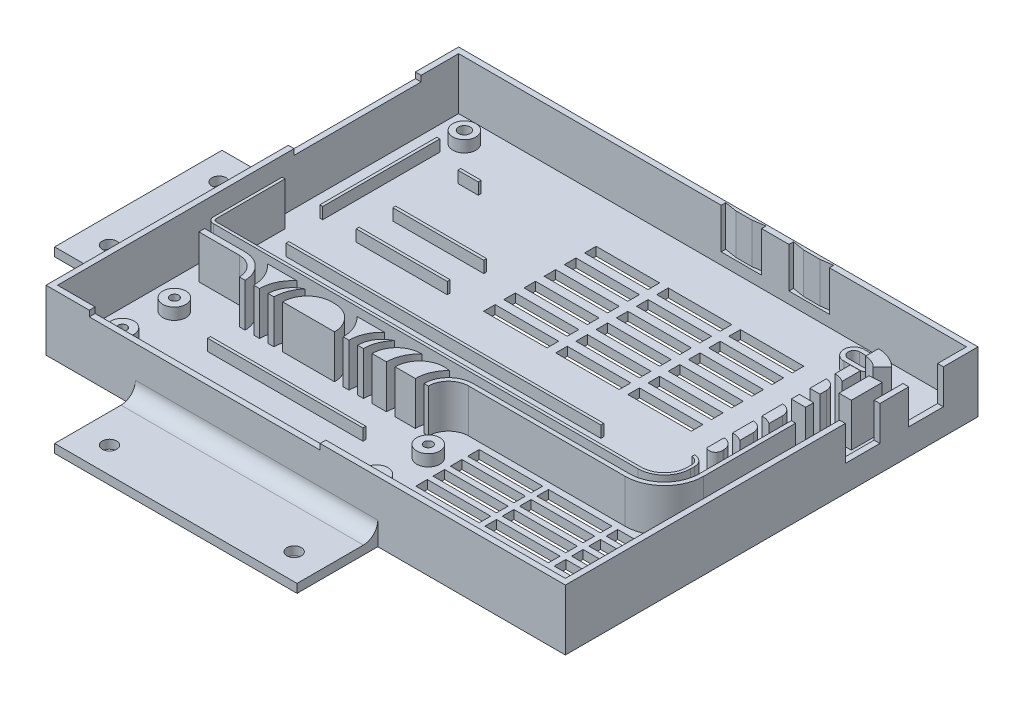
SolidWorks part; units mm, degrees
ref_plane "Front Plane" through (0, 0, 0) normal (0, 0, 1) x (1, 0, 0)
ref_plane "Top Plane" through (0, 0, 0) normal (0, 1, 0) x (1, 0, 0)
ref_plane "Right Plane" through (0, 0, 0) normal (1, 0, 0) x (0, 0, -1)
sketch "Sketch1" plane through (0, 0, 0) normal (0, 1, 0) x (1, 0, 0)
  line L0 (-67.5, 0) -> (67.5, 0) construction
  line L1 (0, 38) -> (0, -38) construction
  line L3 (-67.5, 38) -> (67.5, 38) construction
  line L4 (-67.5, 38) -> (-67.5, -38) construction
  line L5 (-67.5, -38) -> (67.5, -38) construction
  line L6 (67.5, 38) -> (67.5, -38) construction
  line L7 (-67.5, 38) -> (67.5, -38) construction
  line L8 (-67.5, -38) -> (67.5, 38) construction
  line L9 (-71, -71.5) -> (24, -71.5) construction
  line L10 (-23.5, -59) -> (-23.5, -84) construction
  line L11 (-38, -59) -> (-38, -71.5) construction
  line L12 (-17, -59) -> (-17, -71.5) construction
  line L13 (11, -59) -> (11, -71.5) construction
  line L14 (-79.5, 48) -> (-79.5, -95) construction
  line L16 (24, -59) -> (24, -84) construction
  line L17 (-79.5, -95) -> (100.5, -95) construction
  line L18 (100.5, -95) -> (100.5, 48) construction
  line L19 (-71, -59) -> (-71, -84) construction
  line L20 (-71, -84) -> (24, -84) construction
  line L21 (100.5, 48) -> (-79.5, 48) construction
  line L22 (-71, -59) -> (24, -59) construction
  line L23 (0, 38) -> (0, 42) construction
  line L24 (-71.5, 42) -> (71.5, 42) construction
  line L25 (-71.5, 42) -> (-71.5, -42) construction
  line L26 (-71.5, -42) -> (71.5, -42) construction
  line L27 (71.5, 42) -> (71.5, -42) construction
  line L28 (-67.5, 0) -> (-71.5, 0) construction
  line L29 (-43, -59) -> (-43, -71.5) construction
  line L30 (-48, -59) -> (-48, -71.5) construction
  line L31 (-12, -59) -> (-12, -71.5) construction
  line L32 (-7, -59) -> (-7, -71.5) construction
  line L33 (1, -59) -> (1, -71.5) construction
  line L34 (67.5, 38) -> (72.7, 38) construction
  line L35 (67.5, 40) -> (72.7, 40)
  line L36 (67.5, 36) -> (72.7, 36)
  line L37 (67.5, -38) -> (72.6846, -38.4) construction
  line L40 (67.6538, -36.0059) -> (72.8384, -36.4059)
  line L41 (67.3462, -39.9941) -> (72.5307, -40.3941)
  line L42 (-67.5, -38) -> (-67.5, -38.4) construction
  line L43 (-65.5, -38) -> (-65.5, -38.4)
  line L44 (-69.5, -38) -> (-69.5, -38.4)
  circle A0 centre (-67.5, 38) radius 2
  circle A4 centre (-67.5, -62.5) radius 1.5
  circle A8 centre (20.5, -62.5) radius 1.5
  circle A9 centre (20.5, -80.5) radius 1.5
  circle A10 centre (-67.5, -80.5) radius 1.5
  arc A11 (67.5, 40) -> (67.5, 36) centre (67.5, 38) ccw
  arc A12 (72.7, 36) -> (72.7, 40) centre (72.7, 38) ccw
  arc A15 (67.6538, -36.0059) -> (67.3462, -39.9941) centre (67.5, -38) ccw
  arc A16 (72.5307, -40.3941) -> (72.8384, -36.4059) centre (72.6846, -38.4) ccw
  arc A17 (-65.5, -38) -> (-69.5, -38) centre (-67.5, -38) ccw
  arc A18 (-69.5, -38.4) -> (-65.5, -38.4) centre (-67.5, -38.4) ccw
  point P5 (0, 0)
  point P11 (70.1, 38)
  point P13 (-67.5, -38.2)
  point P14 (-23.5, -70)
  point P27 (0, 0)
  point P62 (70.0923, -38.2)
  dimension "D3" = 4
  dimension "D6" = 84
  dimension "D1" = 76
  dimension "D2" = 135
  dimension "D4" = 18
  dimension "D5" = 88
  dimension "D7" = 143
  dimension "D8" = 25
  dimension "D9" = 95
  dimension "D10" = 17
  dimension "D11" = 28
  dimension "D12" = 33
  dimension "D13" = 54
  dimension "D14" = 82
  dimension "D15" = 14.5
  dimension "D16" = 10
  dimension "D17" = 12
  dimension "D18" = 33
  dimension "D19" = 23
  dimension "D20" = 59
  dimension "D21" = 64
  dimension "D22" = 72
  dimension "D23" = 5.2
  dimension "D24" = 4
  dimension "D25" = 4
  dimension "D26" = 5.2
  dimension "D27" = 4
  dimension "D28" = 0.4
  dimension "D29" = 0.4
sketch "CablePath" plane through (0, 0, 0) normal (0, 1, 0) x (1, 0, 0)
  line L0 (-12, -59) -> (-12, -56) construction
  line L5 (101, -94.5) -> (101, 47)
  line L6 (101, 47) -> (-79, 47)
  line L8 (-43, -56) -> (-43, -70.139) construction
  line L9 (-75.5, -42.5222) -> (-75.5, -18.6789) construction
  line L12 (71.5, -29) -> (80.8048, -29) construction
  line L16 (-71.5, -42) -> (71.5, -42) construction
  line L18 (71.5, -18.84) -> (80.8048, -18.84) construction
  line L21 (80.8048, -51.7714) -> (80.8048, 34.0145) construction
  line L22 (30.5, -56) -> (-60.9203, -56) construction
  line L23 (-10.5, -56) -> (-8.5, -56)
  line L24 (71.5, 40.5) -> (71.5, -42) construction
  line L25 (1, -59) -> (1, -56) construction
  line L26 (85.8048, -3.52) -> (85.8048, -35.359) construction
  line L27 (-79, 47) -> (-79, -94.5)
  line L28 (11, -59) -> (11, -56) construction
  line L29 (-79, -94.5) -> (101, -94.5)
  line L30 (-38, -70.139) -> (-38, -56) construction
  line L31 (-43, -59) -> (-43, -71.5) construction
  line L32 (-38, -59) -> (-38, -71.5) construction
  line L33 (71.5, 1.48) -> (80.8048, 1.48) construction
  line L34 (-58, -44.5) -> (-72.0222, -44.5)
  line L35 (75.1637, -46) -> (-33, -46) construction
  line L36 (84.3048, -3.52) -> (84.3048, -8.2028)
  line L37 (-71, -59) -> (24, -59) construction
  line L38 (75.1637, -44.5) -> (-33, -44.5)
  line L39 (71.5, -8.68) -> (80.8048, -8.68) construction
  line L40 (87.3048, -3.52) -> (87.3048, -35.359)
  line L41 (21, -47.5) -> (75.1637, -47.5)
  line L42 (84.3048, -13.68) -> (84.3048, -18.3628)
  line L43 (84.3048, -23.84) -> (84.3048, -24.2165)
  line L44 (84.3048, -3.52) -> (84.3048, -35.359) construction
  line L45 (84.3048, -34) -> (84.3048, -35.359)
  line L46 (-27.8976, -47.4999) -> (-26.899, -47.4999)
  line L47 (75.1637, -47.5) -> (-33, -47.5) construction
  line L48 (2.5, -56) -> (9.5, -56)
  line L49 (-41.5, -56) -> (-39.5, -56)
  line L50 (-36.5, -56) -> (-18.5, -56)
  line L51 (-17, -59) -> (-17, -71.5) construction
  line L52 (21, -49) -> (75.1637, -49)
  line L53 (88.8048, -3.52) -> (88.8048, -35.359)
  line L54 (83.3048, -34) -> (83.3048, -35.359)
  line L55 (75.1637, -43.5) -> (-33, -43.5)
  line L56 (12.5, -56) -> (14, -56)
  line L57 (-58, -46) -> (-72.0222, -46) construction
  line L58 (80.8048, 2.98) -> (80.8048, 5.7849)
  line L59 (80.8048, -0.02) -> (80.8048, -7.18)
  line L60 (80.8048, -10.18) -> (80.8048, -17.34)
  line L61 (80.8048, -20.34) -> (80.8048, -26.2952)
  line L62 (80.8048, -30.5) -> (80.8048, -31.5)
  line L63 (-74, -42.5222) -> (-74, -18.6789)
  line L64 (80.8048, 5.7849) -> (85.7673, 5.7849)
  line L65 (85.7673, 5.7849) -> (85.7673, 2.98)
  line L66 (85.7673, 2.98) -> (80.8048, 2.98)
  line L67 (87.3048, -3.52) -> (88.8048, -3.52)
  line L68 (-7, -59) -> (-7, -56) construction
  line L69 (-17, -59) -> (-17, -56) construction
  line L70 (-48, -59) -> (-48, -56) construction
  line L71 (-58, -43.5) -> (-72.0222, -43.5)
  line L72 (-73, -42.5222) -> (-73, -18.6789)
  line L73 (11, -59) -> (11, -71.5) construction
  line L74 (-58, -47.5) -> (-72.0222, -47.5)
  line L75 (-58, -49.5) -> (-72.0222, -49.5)
  line L76 (-51.5, -56) -> (-49.5, -56)
  line L77 (-72.0222, -47.5) -> (-72.0222, -49.5)
  line L78 (-58, -43.5) -> (-33, -43.5)
  line L79 (-74, -18.6789) -> (-73, -18.6789)
  line L80 (-46.5, -56) -> (-44.5, -56)
  line L81 (-19.2537, -47.5) -> (-9.746, -47.5)
  line L82 (-40.38, -47.1804) -> (-50.62, -47.1804)
  line L83 (-58, -44.5) -> (-33, -44.5)
  line L84 (-15.5, -56) -> (-13.5, -56)
  line L85 (3, -47.5) -> (3.254, -47.5)
  line L86 (-5.5, -56) -> (-0.5, -56)
  line L87 (-71.5, 42) -> (-71.5, -42) construction
  line L88 (67.5, 16.6233) -> (80.8048, 16.6233) construction
  line L89 (67.5, 27.1917) -> (80.8048, 27.1917) construction
  line L90 (67.5, 6.7426) -> (83.9849, 6.7426) construction
  line L91 (85.8048, -3.52) -> (85.8048, 11.6233) construction
  line L92 (85.8048, 11.6233) -> (85.8048, 22.1917) construction
  line L93 (80.8048, 33.1917) -> (80.8048, 28.6917)
  line L94 (85.4191, 26.7697) -> (88.5829, 29.9699)
  line L95 (87.3048, 13.0166) -> (87.3048, 23.4421)
  line L96 (87.3048, 23.4421) -> (91.5804, 23.7236)
  line L97 (84.3065, 23.4421) -> (84.3055, 17.1)
  line L98 (84.3044, 9.4184) -> (80.8048, 9.4184)
  line L99 (80.8048, 9.4184) -> (80.8048, 15.1233)
  line L100 (84.3048, 11.6233) -> (84.3044, 9.4184)
  line L101 (80.8048, 18.1233) -> (80.8048, 23.4421)
  line L102 (91.5804, 23.7236) -> (91.5804, 13.0166)
  line L103 (91.5804, 13.0166) -> (87.3048, 13.0166)
  line L104 (84.3065, 23.4421) -> (80.8048, 23.4421)
  arc A0 (14, -56) -> (21, -49) centre (21, -56) cw
  circle A1 centre (-67.5, -62.5) radius 1.5 construction
  arc A2 (9.5, -56) -> (21, -44.5) centre (21, -56) cw construction
  arc A3 (75.1637, -49) -> (88.8048, -35.359) centre (75.1637, -35.359) ccw
  arc A4 (85.4191, 26.7697) -> (80.8048, 28.6917) centre (80.8048, 22.1917) ccw
  arc A5 (88.5829, 29.9699) -> (80.8048, 33.1917) centre (80.8048, 22.1917) ccw
  arc A7 (84.3055, 17.1) -> (80.8048, 18.1233) centre (80.8048, 11.6233) ccw
  circle A8 centre (-67.5, -80.5) radius 1.5 construction
  circle A9 centre (-67.5, -62.5) radius 1.5
  circle A10 centre (20.5, -62.5) radius 1.5 construction
  circle A11 centre (-67.5, -80.5) radius 1.5
  arc A12 (80.8048, -26.2952) -> (84.3048, -24.2165) centre (82.1448, -24.5655) ccw
  arc A13 (85.8048, 22.1917) -> (80.8048, 27.1917) centre (80.8048, 22.1917) ccw construction
  arc A14 (85.8048, 11.6233) -> (80.8048, 16.6233) centre (80.8048, 11.6233) ccw construction
  arc A15 (84.3048, 11.6233) -> (80.8048, 15.1233) centre (80.8048, 11.6233) ccw
  arc A16 (80.8048, 1.48) -> (85.8048, -3.52) centre (80.8048, -3.52) cw construction
  arc A17 (80.8048, -8.68) -> (85.8048, -13.68) centre (80.8048, -13.68) cw construction
  arc A18 (80.8048, -18.84) -> (85.8048, -23.84) centre (80.8048, -23.84) cw construction
  arc A19 (80.8048, -29) -> (85.8048, -34) centre (80.8048, -34) cw construction
  arc A20 (75.1637, -46) -> (85.8048, -35.359) centre (75.1637, -35.359) ccw construction
  arc A21 (-43, -56) -> (-33, -46) centre (-33, -56) cw construction
  arc A22 (-38, -56) -> (-27.8796, -46) centre (-27.9993, -56) cw construction
  arc A23 (1, -56) -> (11, -46) centre (11, -56) cw construction
  arc A24 (11, -56) -> (21, -46) centre (21, -56) cw construction
  circle A25 centre (20.5, -62.5) radius 1.5
  circle A26 centre (20.5, -80.5) radius 1.5 construction
  circle A27 centre (20.5, -80.5) radius 1.5
  arc A28 (80.8048, -0.02) -> (84.3048, -3.52) centre (80.8048, -3.52) cw
  arc A29 (75.1637, -44.5) -> (84.3048, -35.359) centre (75.1637, -35.359) ccw
  arc A30 (-44.5, -56) -> (-40.38, -47.1804) centre (-33, -56) cw
  arc A31 (80.8048, -10.18) -> (84.3048, -13.68) centre (80.8048, -13.68) cw
  arc A32 (80.8048, -20.34) -> (84.3048, -23.84) centre (80.8048, -23.84) cw
  arc A33 (80.8048, -30.5) -> (84.3048, -34) centre (80.8048, -34) cw
  arc A34 (12.5, -56) -> (21, -47.5) centre (21, -56) cw
  arc A35 (2.5, -56) -> (13, -47.7386) centre (11, -56) cw
  arc A36 (-36.5, -56) -> (-27.8976, -47.4999) centre (-27.9993, -56) cw
  arc A37 (80.8048, 2.98) -> (87.3048, -3.52) centre (80.8048, -3.52) cw construction
  arc A38 (75.1637, -47.5) -> (87.3048, -35.359) centre (75.1637, -35.359) ccw
  arc A39 (-41.5, -56) -> (-36.5004, -48.2542) centre (-33, -56) cw
  arc A40 (80.8048, -7.18) -> (84.3048, -8.2028) centre (80.8048, -13.68) cw
  arc A41 (80.8048, -17.34) -> (84.3048, -18.3628) centre (80.8048, -23.84) cw
  arc A43 (9.5, -56) -> (13, -47.7386) centre (21, -56) cw
  arc A44 (-0.5, -56) -> (3.254, -47.5) centre (11, -56) cw
  arc A45 (-39.5, -56) -> (-36.5004, -48.2542) centre (-27.9993, -56) cw
  arc A46 (-39.5, -56) -> (-27.8617, -44.5001) centre (-27.9993, -56) cw construction
  arc A47 (87.3048, 11.6233) -> (80.8048, 18.1233) centre (80.8048, 11.6233) ccw construction
  arc A48 (80.8048, -7.18) -> (87.3048, -13.68) centre (80.8048, -13.68) cw construction
  arc A49 (80.8048, -17.34) -> (87.3048, -23.84) centre (80.8048, -23.84) cw construction
  arc A50 (80.8048, 4.48) -> (88.8048, -3.52) centre (80.8048, -3.52) cw construction
  arc A51 (-0.5, -56) -> (11, -44.5) centre (11, -56) cw construction
  arc A52 (80.8048, -31.5) -> (83.3048, -34) centre (80.8048, -34) cw
  arc A53 (75.1637, -43.5) -> (83.3048, -35.359) centre (75.1637, -35.359) ccw
  arc A54 (-48, -56) -> (-58, -46) centre (-58, -56) ccw construction
  arc A55 (-17, -56) -> (-26.881, -46) centre (-27.0007, -56) ccw construction
  arc A56 (-41.5, -56) -> (-33, -47.5) centre (-33, -56) cw construction
  arc A57 (-45.5, -56) -> (-33, -43.5) centre (-33, -56) cw construction
  arc A58 (-72.0222, -46) -> (-75.5, -42.5222) centre (-72.0222, -42.5222) cw construction
  arc A59 (-46.5, -56) -> (-50.62, -47.1804) centre (-58, -56) ccw
  arc A60 (-72.0222, -44.5) -> (-74, -42.5222) centre (-72.0222, -42.5222) cw
  arc A61 (-15.5, -56) -> (-19.2537, -47.5) centre (-27.0007, -56) ccw
  arc A62 (-72.0222, -43.5) -> (-73, -42.5222) centre (-72.0222, -42.5222) cw
  arc A63 (-49.5, -56) -> (-58, -47.5) centre (-58, -56) ccw
  arc A64 (-51.5, -56) -> (-58, -49.5) centre (-58, -56) ccw
  arc A65 (-45.5, -56) -> (-58, -43.5) centre (-58, -56) ccw construction
  arc A66 (-18.5, -56) -> (-26.899, -47.4999) centre (-27.0007, -56) ccw
  arc A67 (-12, -56) -> (-2, -46) centre (-2, -56) cw construction
  arc A68 (-15.5, -56) -> (-26.8631, -44.5001) centre (-27.0007, -56) ccw construction
  arc A69 (-46.5, -56) -> (-58, -44.5) centre (-58, -56) ccw construction
  arc A70 (-44.5, -56) -> (-33, -44.5) centre (-33, -56) cw construction
  arc A71 (2.5, -56) -> (11, -47.5) centre (11, -56) cw construction
  arc A72 (-7, -56) -> (3, -46) centre (3, -56) cw construction
  arc A73 (-10.5, -56) -> (-5.5, -48.254) centre (-2, -56) cw
  arc A74 (-5.5, -56) -> (3, -47.5) centre (3, -56) cw
  arc A75 (-13.5, -56) -> (-9.746, -47.5) centre (-2, -56) cw
  arc A76 (-8.5, -56) -> (-5.5, -48.254) centre (3, -56) cw
  arc A77 (87.3048, 22.1917) -> (80.8048, 28.6917) centre (80.8048, 22.1917) ccw construction
  arc A78 (-13.5, -56) -> (-2, -44.5) centre (-2, -56) cw construction
  arc A79 (-10.5, -56) -> (-2, -47.5) centre (-2, -56) cw construction
  arc A80 (91.8048, 22.1917) -> (80.8048, 33.1917) centre (80.8048, 22.1917) ccw construction
  arc A81 (-8.5, -56) -> (3, -44.5) centre (3, -56) cw construction
  point P0 (67.5, -38)
  point P7 (67.5, 38)
  point P10 (-67.5, -80.5)
  point P117 (77.6351, -51.5)
  point P118 (-14.035, -51.5)
  point P127 (77.6351, -54.5)
  point P128 (-14.035, -54.5)
  point P132 (79.6209, -33.364)
  point P134 (85.4849, -33.364)
  point P137 (3.3488, -47.5)
  point P138 (3.3488, -61)
  point P139 (-10.1512, -61)
  point P146 (3.3488, -50.5)
  point P147 (3.3488, -61)
  point P148 (-7.1512, -61)
  point P154 (80.8048, 22.2244)
  point P242 (3.4721, -55.4721)
  point P243 (-8, -55.4721)
  point P244 (3.4721, -44)
  point P253 (87.3048, 22.2244)
  point P256 (80.8048, 22.2244)
  point P257 (91.8048, 22.2244)
  dimension "D5" = 10.16
  dimension "D8" = 3
  dimension "D23" = 1.5
  dimension "D24" = 5
  dimension "D25" = 5
  dimension "D1" = 1.5
  dimension "D3" = 4
  dimension "D4" = 13
  dimension "D6" = 10.16
  dimension "D7" = 10.16
  dimension "D9" = 3.5
  dimension "D10" = 1.5
  dimension "D11" = 1.5
  dimension "D12" = 1
  dimension "D13" = 1.5
  dimension "D14" = 1
  dimension "D15" = 1.5
  dimension "D16" = 2
  dimension "D17" = 1.5
  dimension "D18" = 1.5
  dimension "D28" = 180
  dimension "D19" = 1.5
  dimension "D20" = 1.5
  dimension "D21" = 1.5
  dimension "D22" = 1.5
  dimension "D26" = 1.5
  dimension "D27" = 6
  dimension "D30" = 1.5
  dimension "D31" = 1.5
sketch "Bottom" plane through (0, 0, 0) normal (0, 1, 0) x (1, 0, 0)
  line L0 (-79.5, 48) -> (-79.5, -95) construction
  line L1 (-79.5, 48) -> (-79.5, -95)
  line L2 (-79.5, -95) -> (100.5, -95) construction
  line L3 (-79.5, -95) -> (100.5, -95)
  line L4 (67.6538, -36.0059) -> (72.8384, -36.4059) construction
  line L5 (67.3462, -39.9941) -> (72.5307, -40.3941) construction
  line L6 (100.5, -95) -> (100.5, 48) construction
  line L7 (100.5, -95) -> (100.5, 48)
  line L8 (100.5, 48) -> (-79.5, 48) construction
  line L9 (100.5, 48) -> (-79.5, 48)
  line L10 (67.6538, -36.0059) -> (72.8384, -36.4059)
  line L11 (67.3462, -39.9941) -> (72.5307, -40.3941)
  line L12 (67.5, 36) -> (72.7, 36) construction
  line L13 (67.5, 40) -> (72.7, 40) construction
  line L14 (67.5, 36) -> (72.7, 36)
  line L15 (67.5, 40) -> (72.7, 40)
  line L16 (-65.5, -38) -> (-65.5, -38.4) construction
  line L17 (-69.5, -38) -> (-69.5, -38.4) construction
  line L18 (-65.5, -38) -> (-65.5, -38.4)
  line L19 (-69.5, -38) -> (-69.5, -38.4)
  arc A0 (72.5307, -40.3941) -> (72.8384, -36.4059) centre (72.6846, -38.4) ccw construction
  arc A1 (67.6538, -36.0059) -> (67.3462, -39.9941) centre (67.5, -38) ccw construction
  arc A2 (72.5307, -40.3941) -> (72.8384, -36.4059) centre (72.6846, -38.4) ccw
  arc A3 (67.6538, -36.0059) -> (67.3462, -39.9941) centre (67.5, -38) ccw
  arc A4 (72.7, 36) -> (72.7, 40) centre (72.7, 38) ccw construction
  arc A5 (67.5, 40) -> (67.5, 36) centre (67.5, 38) ccw construction
  arc A6 (72.7, 36) -> (72.7, 40) centre (72.7, 38) ccw
  arc A7 (67.5, 40) -> (67.5, 36) centre (67.5, 38) ccw
  circle A8 centre (-67.5, 38) radius 2 construction
  circle A9 centre (-67.5, 38) radius 2
  arc A10 (-69.5, -38.4) -> (-65.5, -38.4) centre (-67.5, -38.4) ccw construction
  arc A11 (-65.5, -38) -> (-69.5, -38) centre (-67.5, -38) ccw construction
  arc A12 (-69.5, -38.4) -> (-65.5, -38.4) centre (-67.5, -38.4) ccw
  arc A13 (-65.5, -38) -> (-69.5, -38) centre (-67.5, -38) ccw
  dimension "D1" = 143
  dimension "D2" = 180
extrude "Boss-Bottom" add sketch "Bottom" along normal blind 3
sketch "PCBmount" plane through (0, 3, 0) normal (0, 1, 0) x (1, 0, 0)
  line L0 (-49.5761, -67.9069) -> (-49.5761, -68.9069)
  line L1 (-49.5761, -67.9069) -> (4.2504, -67.9069)
  line L2 (-49.5761, -68.9069) -> (4.2504, -68.9069)
  line L3 (4.2504, -67.9069) -> (4.2504, -68.9069)
  line L5 (-64.5007, -25.8146) -> (44.6202, -25.8146)
  line L6 (-64.5007, -25.8146) -> (-64.5007, -26.8146)
  line L7 (44.6202, -25.8146) -> (44.6202, -26.8146)
  line L8 (-64.5007, -26.8146) -> (44.6202, -26.8146)
  line L9 (-56.6714, -10.3272) -> (-25.1095, -10.3272)
  line L10 (-56.6714, -10.3272) -> (-56.6714, -9.3272)
  line L11 (-25.1095, -10.3272) -> (-25.1095, -9.3272)
  line L12 (-56.6714, -9.3272) -> (-25.1095, -9.3272)
  line L13 (-56.6714, 2.3448) -> (-25.1095, 2.3448)
  line L14 (-56.6714, 2.3448) -> (-56.6714, 3.3448)
  line L15 (-25.1095, 2.3448) -> (-25.1095, 3.3448)
  line L16 (-56.6714, 3.3448) -> (-25.1095, 3.3448)
  line L17 (-70.1846, -9.4098) -> (-69.1846, -9.4098)
  line L18 (-70.1846, -9.4098) -> (-70.1846, 31.1536)
  line L19 (-69.1846, -9.4098) -> (-69.1846, 31.1536)
  line L20 (-70.1846, 31.1536) -> (-69.1846, 31.1536)
  line L21 (-56.6714, 24.8918) -> (-49.5761, 24.8918)
  line L22 (-56.6714, 24.8918) -> (-56.6714, 25.8918)
  line L23 (-49.5761, 24.8918) -> (-49.5761, 25.8918)
  line L24 (-56.6714, 25.8918) -> (-49.5761, 25.8918)
  line L30 (67.5, 36) -> (72.7, 36) construction
  line L31 (67.5, 40) -> (72.7, 40) construction
  line L32 (-67.5, 0) -> (67.5, 0) construction
  line L33 (-67.5, 0) -> (67.5, 0) construction
  line L34 (67.5, 36) -> (72.7, 36)
  line L35 (67.5, 40) -> (72.7, 40)
  line L38 (-65.5, -38) -> (-65.5, -38.4) construction
  line L39 (-69.5, -38) -> (-69.5, -38.4) construction
  line L40 (-65.5, -38) -> (-65.5, -38.4)
  line L41 (-69.5, -38) -> (-69.5, -38.4)
  line L42 (-64, -38) -> (-64, -38.4)
  line L43 (-71, -38) -> (-71, -38.4)
  line L44 (67.5, 34.5) -> (72.7, 34.5)
  line L45 (67.5, 41.5) -> (72.7, 41.5)
  line L46 (67.6538, -36.0059) -> (72.8384, -36.4059) construction
  line L47 (67.3462, -39.9941) -> (72.5307, -40.3941) construction
  line L48 (67.6538, -36.0059) -> (72.8384, -36.4059)
  line L49 (67.3462, -39.9941) -> (72.5307, -40.3941)
  line L50 (67.7692, -34.5104) -> (72.9538, -34.9104)
  line L51 (67.2308, -41.4896) -> (72.4154, -41.8896)
  circle A4 centre (-67.5, -62.5) radius 1.5 construction
  circle A6 centre (-67.5, 38) radius 2 construction
  circle A8 centre (20.5, -80.5) radius 1.5 construction
  circle A9 centre (20.5, -62.5) radius 1.5 construction
  arc A10 (72.7, 36) -> (72.7, 40) centre (72.7, 38) ccw construction
  circle A11 centre (-67.5, -80.5) radius 1.5 construction
  circle A12 centre (-67.5, -62.5) radius 1.5
  arc A13 (-65.5, -38) -> (-69.5, -38) centre (-67.5, -38) ccw construction
  circle A14 centre (-67.5, 38) radius 2
  circle A16 centre (-67.5, 38) radius 4
  arc A17 (67.5, 40) -> (67.5, 36) centre (67.5, 38) ccw construction
  arc A18 (72.7, 36) -> (72.7, 40) centre (72.7, 38) ccw
  arc A19 (-69.5, -38.4) -> (-65.5, -38.4) centre (-67.5, -38.4) ccw construction
  circle A20 centre (-67.5, -62.5) radius 4
  circle A21 centre (-67.5, -80.5) radius 4
  circle A22 centre (20.5, -80.5) radius 4
  circle A23 centre (20.5, -62.5) radius 4
  circle A24 centre (-67.5, -80.5) radius 1.5
  circle A25 centre (20.5, -80.5) radius 1.5
  circle A26 centre (20.5, -62.5) radius 1.5
  arc A27 (67.5, 40) -> (67.5, 36) centre (67.5, 38) ccw
  arc A30 (-65.5, -38) -> (-69.5, -38) centre (-67.5, -38) ccw
  arc A31 (-69.5, -38.4) -> (-65.5, -38.4) centre (-67.5, -38.4) ccw
  arc A32 (-71, -38.4) -> (-64, -38.4) centre (-67.5, -38.4) ccw
  arc A33 (-64, -38) -> (-71, -38) centre (-67.5, -38) ccw
  arc A34 (72.7, 34.5) -> (72.7, 41.5) centre (72.7, 38) ccw
  arc A35 (67.5, 41.5) -> (67.5, 34.5) centre (67.5, 38) ccw
  arc A36 (72.5307, -40.3941) -> (72.8384, -36.4059) centre (72.6846, -38.4) ccw construction
  arc A37 (67.6538, -36.0059) -> (67.3462, -39.9941) centre (67.5, -38) ccw construction
  arc A38 (72.5307, -40.3941) -> (72.8384, -36.4059) centre (72.6846, -38.4) ccw
  arc A39 (67.6538, -36.0059) -> (67.3462, -39.9941) centre (67.5, -38) ccw
  arc A40 (72.4154, -41.8896) -> (72.9538, -34.9104) centre (72.6846, -38.4) ccw
  arc A41 (67.7692, -34.5104) -> (67.2308, -41.4896) centre (67.5, -38) ccw
  dimension "D1" = 8
  dimension "D2" = 8
  dimension "D3" = 1
  dimension "D5" = 1.5
  dimension "D6" = 1.5
  dimension "D4" = 1.5
extrude "Boss-PCBmount" add sketch "PCBmount" along normal blind 4
sketch "Sides" plane through (0, 3, 0) normal (0, 1, 0) x (1, 0, 0)
  line L0 (-79.5, -95) -> (100.5, -95) construction
  line L1 (100.5, -95) -> (100.5, 48) construction
  line L2 (-79.5, 48) -> (-79.5, -95) construction
  line L3 (100.5, 48) -> (-79.5, 48) construction
  line L4 (-79.5, -95) -> (100.5, -95)
  line L5 (100.5, -95) -> (100.5, 48)
  line L6 (-79.5, 48) -> (-79.5, -95)
  line L7 (100.5, 48) -> (-79.5, 48)
  line L8 (-77.5, -93) -> (98.5, -93)
  line L9 (98.5, -93) -> (98.5, 46)
  line L10 (98.5, 46) -> (-77.5, 46)
  line L11 (-77.5, 46) -> (-77.5, -93)
  dimension "D1" = 2
extrude "Boss-Sides" add sketch "Sides" along normal blind 18
sketch "24VHeatBed" plane through (100.5, 0, 0) normal (1, 0, 0) x (0, 0, -1)
  line L0 (36, 21) -> (36, 9)
  line L1 (48, 21) -> (48, 0) construction
  line L2 (36, 9) -> (24, 9)
  line L3 (24, 9) -> (24, 21)
  line L4 (24, 21) -> (36, 21)
  line L5 (14, 21) -> (14, 9)
  line L6 (14, 9) -> (2, 9)
  line L7 (2, 9) -> (2, 21)
  line L8 (2, 21) -> (14, 21)
  line L10 (-95, 21) -> (48, 21) construction
  dimension "D3" = 12
  dimension "D5" = 12
  dimension "D6" = 10
extrude "Cut-24VHeatBed" cut sketch "24VHeatBed" against normal up to surface (2 mm away) up to face at (98.5, 12, 23.5)
extrude "Boss-CablePath" add sketch "CablePath" along normal blind 18 contours A74 L85 A44 L86 | A76 A73 L23 | A75 L81 A61 L84 | L38 L83 L34 A60 L63 L79 L72 A62 L71 L78 L55 A53 L54 A52 L62 A33 L45 A29 | A66 L46 A36 L50 | A35 A43 L48 | A34 L41 A38 L40 L67 L53 A3 L52 A0 L56 | L75 L77 L74 A63 L76 A64 | A59 L82 A30 L80 | A39 A45 L49 | L43 A12 L61 A32 | L42 A41 L60 A31 | L36 A40 L59 A28 | L65 L66 L58 L64 | L100 L98 L99 A15 | L97 A7 L101 L104 | L93 A4 L94 A5 | L102 L103 L95 L96
sketch "Fan" plane through (0, 3, 0) normal (0, 1, 0) x (1, 0, 0)
  line L1 (55.5, -50) -> (95.5, -50) construction
  line L2 (55.5, -50) -> (55.5, -90) construction
  line L3 (55.5, -90) -> (95.5, -90) construction
  line L4 (95.5, -50) -> (95.5, -90) construction
  line L5 (55.5, -50) -> (95.5, -90) construction
  line L6 (55.5, -90) -> (95.5, -50) construction
  line L8 (98.5, -93) -> (98.5, 2) construction
  line L9 (-77.5, -93) -> (98.5, -93) construction
  circle A0 centre (75.5, -70) radius 19
  circle A1 centre (75.5, -70) radius 10
  arc A2 (75.5, -70) -> (75.5, -51) centre (80.3261, -60.5) cw
  arc A3 (75.5, -70) -> (91.9545, -60.5) centre (86.1403, -69.4295) cw
  arc A4 (75.5, -70) -> (91.9545, -79.5) centre (81.3142, -78.9295) cw
  arc A5 (75.5, -70) -> (75.5, -89) centre (70.6739, -79.5) cw
  arc A6 (75.5, -70) -> (59.0455, -79.5) centre (64.8597, -70.5705) cw
  arc A7 (75.5, -70) -> (59.0455, -60.5) centre (69.6858, -61.0705) cw
  point P0 (75.5, -70)
  point P27 (75.5, -70)
  dimension "D5" = 38
  dimension "D6" = 20
  dimension "D1" = 40
  dimension "D2" = 40
  dimension "D3" = 3
  dimension "D4" = 3
  dimension "D7" = 6
sketch "FanHoles" plane through (0, 0, 0) normal (0, -1, 0) x (1, 0, 0)
  line L0 (55.5, 90) -> (95.5, 50) construction
  line L1 (55.5, 90) -> (95.5, 50) construction
  line L2 (55.5, 50) -> (95.5, 90) construction
  line L3 (55.5, 50) -> (95.5, 90) construction
  line L4 (55.5, 50) -> (95.5, 50) construction
  line L5 (55.5, 50) -> (95.5, 50) construction
  line L6 (55.5, 90) -> (95.5, 90) construction
  line L7 (55.5, 90) -> (95.5, 90) construction
  line L8 (55.5, 50) -> (55.5, 90) construction
  line L9 (55.5, 50) -> (55.5, 90) construction
  line L10 (95.5, 50) -> (95.5, 90) construction
  line L11 (95.5, 50) -> (95.5, 90) construction
  line L12 (75.5, 50) -> (75.5, 90) construction
  line L13 (55.5, 70) -> (95.5, 70) construction
  circle A1 centre (59.5, 54) radius 1.5
  circle A2 centre (59.5, 86) radius 1.5
  circle A6 centre (91.5, 86) radius 1.5
  circle A7 centre (91.5, 54) radius 1.5
  dimension "D1" = 32
  dimension "D2" = 32
sketch "ExtruderCables" plane through (0, 0, 95) normal (0, 0, 1) x (1, 0, 0)
  line L0 (-79.5, 21) -> (-79.5, 0) construction
  line L1 (-64.5, 21) -> (15.5, 21)
  line L2 (-64.5, 21) -> (-64.5, 19)
  line L3 (-64.5, 19) -> (15.5, 19)
  line L4 (15.5, 21) -> (15.5, 19)
  line L5 (-64.5, 21) -> (15.5, 19) construction
  line L6 (-64.5, 19) -> (15.5, 21) construction
  line L7 (-79.5, 21) -> (100.5, 21) construction
  point P0 (-24.5, 20)
  dimension "D1" = 15
  dimension "D2" = 80
extrude "Cut-ExtruderCables" cut sketch "ExtruderCables" against normal up to surface (2 mm away) up to face at (10.5, 12, 93)
sketch "LCD" plane through (-79.5, 0, 0) normal (-1, 0, 0) x (0, 0, 1)
  line L0 (-33, 21) -> (-33, 19)
  line L1 (-33, 21) -> (11, 21)
  line L2 (-33, 19) -> (11, 19)
  line L3 (11, 21) -> (11, 19)
  line L4 (-48, 21) -> (95, 21) construction
  line L5 (-48, 21) -> (-48, 0) construction
  dimension "D1" = 15
  dimension "D2" = 59
extrude "Cut-LCD" cut sketch "LCD" against normal up to surface (2 mm away) up to face at (-77.5, 12, 23.5)
sketch "Sketch2" plane through (0, 0, 0) normal (0, -1, 0) x (1, 0, 0)
  line L0 (-79.5, -48) -> (-79.5, 95) construction
  line L3 (-79.5, 95) -> (100.5, 95) construction
  line L4 (35.5, 123) -> (35.5, 95)
  line L5 (-98.5, -48) -> (-98.5, 143.5262) construction
  line L6 (-104.4968, 114) -> (115.2818, 114) construction
  line L7 (35.5, 123) -> (-48.5, 123)
  line L8 (-107.5, 64) -> (-107.5, 6)
  line L9 (35.5, 95) -> (-48.5, 95)
  line L10 (-79.5, 64) -> (-79.5, 6)
  line L11 (-48.5, 95) -> (-48.5, 123)
  line L13 (-79.5, 6) -> (-107.5, 6)
  line L14 (-107.5, 64) -> (-79.5, 64)
  line L15 (-79.5, 95) -> (-79.5, 123) construction
  line L16 (-79.5, 95) -> (-116.8086, 95) construction
  line L17 (-107.5, 95) -> (-107.5, 123) construction
  line L18 (-107.5, 123) -> (-79.5, 123) construction
  circle A0 centre (-98.5, 16) radius 2.5
  circle A1 centre (-98.5, 54) radius 2.5
  circle A2 centre (-38.5, 114) radius 2.5
  circle A3 centre (25.5, 114) radius 2.5
  dimension "D2" = 28
  dimension "D4" = 60
  dimension "D5" = 60
  dimension "D12" = 10
  dimension "D3" = 38
  dimension "D6" = 64
  dimension "D7" = 28
  dimension "D8" = 9
  dimension "D9" = 9
  dimension "D10" = 10
  dimension "D11" = 10
  dimension "D13" = 10
extrude "Boss-Extrude1" add sketch "Sketch2" against normal blind 3
fillet "Fillet1" radius 5 2 edges at (-79.5, 3, 35) (-6.5, 3, 95)
sketch "USB" plane through (0, 21, 0) normal (0, 1, 0) x (1, 0, 0)
  line L0 (37, 46) -> (51, 46)
  line L1 (98.5, 46) -> (-77.5, 46) construction
  line L2 (51, 46) -> (51, 47.4707)
  line L3 (4.6819, 46.8766) -> (57.5762, 46.8766) construction
  line L4 (13.5, 47.5631) -> (17.6913, 46.8766)
  line L5 (37, 47.5631) -> (41.1913, 46.8766)
  line L6 (37, 47.5631) -> (37, 46)
  line L7 (100.5, 36) -> (100.5, 48) construction
  line L8 (27.5, 46) -> (13.5, 46)
  line L9 (13.5, 46) -> (13.5, 47.5631)
  line L10 (27.5, 47.5504) -> (23.3067, 46.8766)
  line L11 (51, 47.4707) -> (46.7946, 46.8766)
  line L12 (17.6913, 46.8766) -> (23.3067, 46.8766)
  line L13 (27.5, 47.5504) -> (27.5, 46)
  line L14 (41.1913, 46.8766) -> (46.7946, 46.8766)
  dimension "D1" = 14
  dimension "D2" = 49.5
  dimension "D3" = 73
extrude "Cut-USB" cut sketch "USB" against normal blind 14
sketch "Sketch3" plane through (0, 3, 0) normal (0, 1, 0) x (1, 0, 0)
  line L0 (50.8814, -87.2405) -> (72.8814, -87.2405)
  line L1 (74.8814, -87.2405) -> (96.8814, -87.2405)
  line L2 (74.8814, -87.2405) -> (74.8814, -91.2405)
  line L3 (74.8814, -91.2405) -> (96.8814, -91.2405)
  line L4 (96.8814, -87.2405) -> (96.8814, -91.2405)
  line L5 (74.8814, -87.2405) -> (96.8814, -91.2405) construction
  line L6 (74.8814, -91.2405) -> (96.8814, -87.2405) construction
  line L7 (50.8814, -87.2405) -> (50.8814, -91.2405)
  line L8 (50.8814, -91.2405) -> (72.8814, -91.2405)
  line L9 (72.8814, -87.2405) -> (72.8814, -91.2405)
  line L10 (26.8814, -87.2405) -> (48.8814, -87.2405)
  line L11 (26.8814, -87.2405) -> (26.8814, -91.2405)
  line L12 (26.8814, -91.2405) -> (48.8814, -91.2405)
  line L13 (48.8814, -87.2405) -> (48.8814, -91.2405)
  line L14 (50.8814, -81.2405) -> (72.8814, -81.2405)
  line L15 (50.8814, -81.2405) -> (50.8814, -85.2405)
  line L16 (50.8814, -85.2405) -> (72.8814, -85.2405)
  line L17 (72.8814, -81.2405) -> (72.8814, -85.2405)
  line L18 (26.8814, -81.2405) -> (48.8814, -81.2405)
  line L19 (26.8814, -81.2405) -> (26.8814, -85.2405)
  line L20 (26.8814, -85.2405) -> (48.8814, -85.2405)
  line L21 (48.8814, -81.2405) -> (48.8814, -85.2405)
  line L22 (50.8814, -75.2405) -> (72.8814, -75.2405)
  line L23 (50.8814, -75.2405) -> (50.8814, -79.2405)
  line L24 (50.8814, -79.2405) -> (72.8814, -79.2405)
  line L25 (72.8814, -75.2405) -> (72.8814, -79.2405)
  line L26 (26.8814, -75.2405) -> (48.8814, -75.2405)
  line L27 (26.8814, -75.2405) -> (26.8814, -79.2405)
  line L28 (26.8814, -79.2405) -> (48.8814, -79.2405)
  line L29 (48.8814, -75.2405) -> (48.8814, -79.2405)
  line L30 (50.8814, -69.2405) -> (72.8814, -69.2405)
  line L31 (50.8814, -69.2405) -> (50.8814, -73.2405)
  line L32 (50.8814, -73.2405) -> (72.8814, -73.2405)
  line L33 (72.8814, -69.2405) -> (72.8814, -73.2405)
  line L34 (26.8814, -69.2405) -> (48.8814, -69.2405)
  line L35 (26.8814, -69.2405) -> (26.8814, -73.2405)
  line L36 (26.8814, -73.2405) -> (48.8814, -73.2405)
  line L37 (48.8814, -69.2405) -> (48.8814, -73.2405)
  line L38 (50.8814, -63.2405) -> (72.8814, -63.2405)
  line L39 (50.8814, -63.2405) -> (50.8814, -67.2405)
  line L40 (50.8814, -67.2405) -> (72.8814, -67.2405)
  line L41 (72.8814, -63.2405) -> (72.8814, -67.2405)
  line L42 (26.8814, -63.2405) -> (48.8814, -63.2405)
  line L43 (26.8814, -63.2405) -> (26.8814, -67.2405)
  line L44 (26.8814, -67.2405) -> (48.8814, -67.2405)
  line L45 (48.8814, -63.2405) -> (48.8814, -67.2405)
  line L46 (74.8814, -81.2405) -> (96.8814, -81.2405)
  line L47 (74.8814, -81.2405) -> (74.8814, -85.2405)
  line L48 (74.8814, -85.2405) -> (96.8814, -85.2405)
  line L49 (96.8814, -81.2405) -> (96.8814, -85.2405)
  line L50 (74.8814, -75.2405) -> (96.8814, -75.2405)
  line L51 (74.8814, -75.2405) -> (74.8814, -79.2405)
  line L52 (74.8814, -79.2405) -> (96.8814, -79.2405)
  line L53 (96.8814, -75.2405) -> (96.8814, -79.2405)
  line L54 (74.8814, -69.2405) -> (96.8814, -69.2405)
  line L55 (74.8814, -69.2405) -> (74.8814, -73.2405)
  line L56 (74.8814, -73.2405) -> (96.8814, -73.2405)
  line L57 (96.8814, -69.2405) -> (96.8814, -73.2405)
  line L58 (74.8814, -63.2405) -> (96.8814, -63.2405)
  line L59 (74.8814, -63.2405) -> (74.8814, -67.2405)
  line L60 (74.8814, -67.2405) -> (96.8814, -67.2405)
  line L61 (96.8814, -63.2405) -> (96.8814, -67.2405)
  line L62 (74.8814, -57.2405) -> (96.8814, -57.2405)
  line L63 (74.8814, -57.2405) -> (74.8814, -61.2405)
  line L64 (74.8814, -61.2405) -> (96.8814, -61.2405)
  line L65 (96.8814, -57.2405) -> (96.8814, -61.2405)
  line L66 (50.8814, -57.2405) -> (72.8814, -57.2405)
  line L67 (50.8814, -57.2405) -> (50.8814, -61.2405)
  line L68 (50.8814, -61.2405) -> (72.8814, -61.2405)
  line L69 (72.8814, -57.2405) -> (72.8814, -61.2405)
  line L70 (26.8814, -57.2405) -> (48.8814, -57.2405)
  line L71 (26.8814, -57.2405) -> (26.8814, -61.2405)
  line L72 (26.8814, -61.2405) -> (48.8814, -61.2405)
  line L73 (48.8814, -57.2405) -> (48.8814, -61.2405)
  line L74 (74.8814, -51.2405) -> (96.8814, -51.2405)
  line L75 (74.8814, -51.2405) -> (74.8814, -55.2405)
  line L76 (74.8814, -55.2405) -> (96.8814, -55.2405)
  line L77 (96.8814, -51.2405) -> (96.8814, -55.2405)
  line L78 (50.8814, -51.2405) -> (72.8814, -51.2405)
  line L79 (50.8814, -51.2405) -> (50.8814, -55.2405)
  line L80 (50.8814, -55.2405) -> (72.8814, -55.2405)
  line L81 (72.8814, -51.2405) -> (72.8814, -55.2405)
  line L82 (26.8814, -51.2405) -> (48.8814, -51.2405)
  line L83 (26.8814, -51.2405) -> (26.8814, -55.2405)
  line L84 (26.8814, -55.2405) -> (48.8814, -55.2405)
  line L85 (48.8814, -51.2405) -> (48.8814, -55.2405)
  line L86 (11.148, 26.0057) -> (33.148, 26.0057)
  line L87 (-13.852, 30.0057) -> (8.148, 30.0057)
  line L88 (-13.852, 30.0057) -> (-13.852, 26.0057)
  line L89 (-13.852, 26.0057) -> (8.148, 26.0057)
  line L90 (8.148, 30.0057) -> (8.148, 26.0057)
  line L91 (-13.852, 30.0057) -> (8.148, 26.0057) construction
  line L92 (-13.852, 26.0057) -> (8.148, 30.0057) construction
  line L93 (11.148, 30.0057) -> (33.148, 30.0057)
  line L94 (33.148, 30.0057) -> (33.148, 26.0057)
  line L95 (11.148, 30.0057) -> (11.148, 26.0057)
  line L96 (36.148, 26.0057) -> (58.148, 26.0057)
  line L97 (36.148, 30.0057) -> (58.148, 30.0057)
  line L98 (58.148, 30.0057) -> (58.148, 26.0057)
  line L99 (36.148, 30.0057) -> (36.148, 26.0057)
  line L100 (11.148, 19.0057) -> (33.148, 19.0057)
  line L101 (11.148, 23.0057) -> (33.148, 23.0057)
  line L102 (33.148, 23.0057) -> (33.148, 19.0057)
  line L103 (11.148, 23.0057) -> (11.148, 19.0057)
  line L104 (36.148, 19.0057) -> (58.148, 19.0057)
  line L105 (36.148, 23.0057) -> (58.148, 23.0057)
  line L106 (58.148, 23.0057) -> (58.148, 19.0057)
  line L107 (36.148, 23.0057) -> (36.148, 19.0057)
  line L108 (11.148, 12.0057) -> (33.148, 12.0057)
  line L109 (11.148, 16.0057) -> (33.148, 16.0057)
  line L110 (33.148, 16.0057) -> (33.148, 12.0057)
  line L111 (11.148, 16.0057) -> (11.148, 12.0057)
  line L112 (36.148, 12.0057) -> (58.148, 12.0057)
  line L113 (36.148, 16.0057) -> (58.148, 16.0057)
  line L114 (58.148, 16.0057) -> (58.148, 12.0057)
  line L115 (36.148, 16.0057) -> (36.148, 12.0057)
  line L116 (11.148, 5.0057) -> (33.148, 5.0057)
  line L117 (11.148, 9.0057) -> (33.148, 9.0057)
  line L118 (33.148, 9.0057) -> (33.148, 5.0057)
  line L119 (11.148, 9.0057) -> (11.148, 5.0057)
  line L120 (36.148, 5.0057) -> (58.148, 5.0057)
  line L121 (36.148, 9.0057) -> (58.148, 9.0057)
  line L122 (58.148, 9.0057) -> (58.148, 5.0057)
  line L123 (36.148, 9.0057) -> (36.148, 5.0057)
  line L124 (11.148, -1.9943) -> (33.148, -1.9943)
  line L125 (11.148, 2.0057) -> (33.148, 2.0057)
  line L126 (33.148, 2.0057) -> (33.148, -1.9943)
  line L127 (11.148, 2.0057) -> (11.148, -1.9943)
  line L128 (36.148, -1.9943) -> (58.148, -1.9943)
  line L129 (36.148, 2.0057) -> (58.148, 2.0057)
  line L130 (58.148, 2.0057) -> (58.148, -1.9943)
  line L131 (36.148, 2.0057) -> (36.148, -1.9943)
  line L132 (11.148, -8.9943) -> (33.148, -8.9943)
  line L133 (11.148, -4.9943) -> (33.148, -4.9943)
  line L134 (33.148, -4.9943) -> (33.148, -8.9943)
  line L135 (11.148, -4.9943) -> (11.148, -8.9943)
  line L136 (36.148, -8.9943) -> (58.148, -8.9943)
  line L137 (36.148, -4.9943) -> (58.148, -4.9943)
  line L138 (58.148, -4.9943) -> (58.148, -8.9943)
  line L139 (36.148, -4.9943) -> (36.148, -8.9943)
  line L140 (-13.852, 19.0057) -> (8.148, 19.0057)
  line L141 (-13.852, 23.0057) -> (8.148, 23.0057)
  line L142 (8.148, 23.0057) -> (8.148, 19.0057)
  line L143 (-13.852, 23.0057) -> (-13.852, 19.0057)
  line L144 (-13.852, 12.0057) -> (8.148, 12.0057)
  line L145 (-13.852, 16.0057) -> (8.148, 16.0057)
  line L146 (8.148, 16.0057) -> (8.148, 12.0057)
  line L147 (-13.852, 16.0057) -> (-13.852, 12.0057)
  line L148 (-13.852, 5.0057) -> (8.148, 5.0057)
  line L149 (-13.852, 9.0057) -> (8.148, 9.0057)
  line L150 (8.148, 9.0057) -> (8.148, 5.0057)
  line L151 (-13.852, 9.0057) -> (-13.852, 5.0057)
  line L152 (-13.852, -1.9943) -> (8.148, -1.9943)
  line L153 (-13.852, 2.0057) -> (8.148, 2.0057)
  line L154 (8.148, 2.0057) -> (8.148, -1.9943)
  line L155 (-13.852, 2.0057) -> (-13.852, -1.9943)
  line L156 (-13.852, -8.9943) -> (8.148, -8.9943)
  line L157 (-13.852, -4.9943) -> (8.148, -4.9943)
  line L158 (8.148, -4.9943) -> (8.148, -8.9943)
  line L159 (-13.852, -4.9943) -> (-13.852, -8.9943)
  point P0 (85.8814, -89.2405)
  point P5 (-2.852, 28.0057)
  point P91 (22.148, 28.0057)
  point P97 (47.148, 28.0057)
  point P102 (22.148, 21.0057)
  point P107 (47.148, 21.0057)
  point P112 (22.148, 14.0057)
  point P117 (47.148, 14.0057)
  point P122 (22.148, 7.0057)
  point P127 (47.148, 7.0057)
  point P132 (22.148, 0.0057)
  point P137 (47.148, 0.0057)
  point P142 (22.148, -6.9943)
  point P147 (47.148, -6.9943)
  point P152 (-2.852, 21.0057)
  point P157 (-2.852, 14.0057)
  point P162 (-2.852, 7.0057)
  point P167 (-2.852, 0.0057)
  point P172 (-2.852, -6.9943)
  dimension "D3" = 22
  dimension "D4" = 4
  dimension "D5" = 22
  dimension "D6" = 4
  dimension "D1" = 3
  dimension "D2" = 7
  dimension "D7" = 3
  dimension "D8" = 6
extrude "Cut-Extrude1" cut sketch "Sketch3" against normal blind 10
